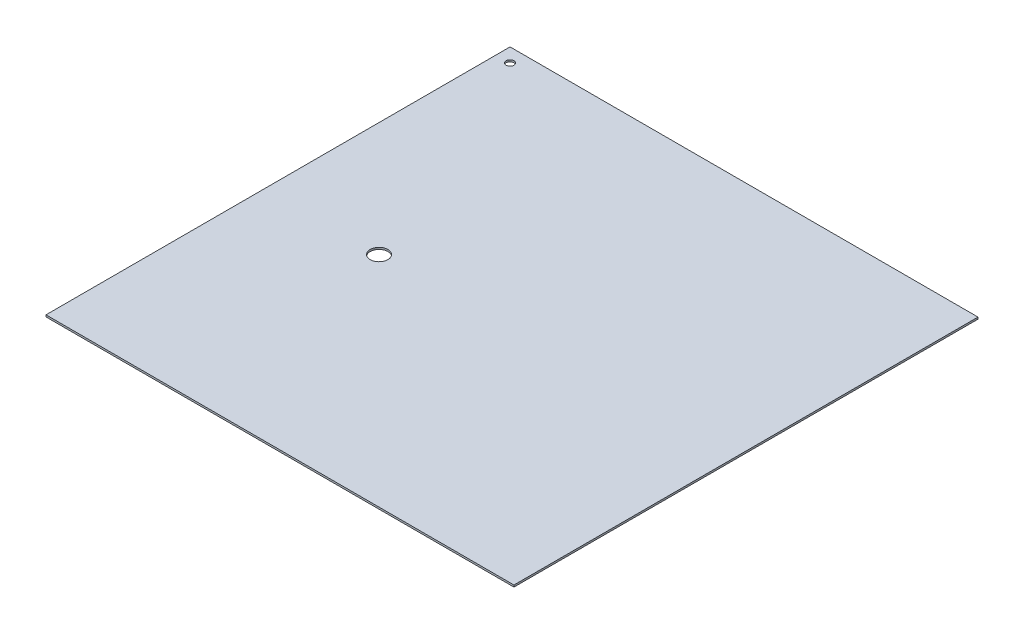
SolidWorks part; units mm, degrees
ref_plane "Front Plane" through (0, 0, 0) normal (0, 0, 1) x (1, 0, 0)
ref_plane "Top Plane" through (0, 0, 0) normal (0, 1, 0) x (1, 0, 0)
ref_plane "Right Plane" through (0, 0, 0) normal (1, 0, 0) x (0, 0, -1)
sketch "Sketch1" plane through (0, 0, 0) normal (0, 0, 1) x (1, 0, 0)
  line L0 (0, 0.3969) -> (0, -0.3969)
  line L1 (-152.4, 0) -> (152.4, 0) construction
  point P6 (0, 0)
  dimension "Width" = 304.8
  dimension "Thk" = 0.7937
sketch "Sketch2" plane through (0, 0, 0) normal (1, 0, 0) x (0, 0, -1)
  line L0 (152.4, 0) -> (-152.4, 0)
  point P4 (0, 0)
  dimension "Length" = 304.8
sketch "Sketch3" plane through (0, 0, 0) normal (0, 0, 1) x (1, 0, 0)
  line L1 (152.4, 0.3969) -> (-152.4, 0.3969)
  line L2 (152.4, 0.3969) -> (152.4, -0.3969)
  line L3 (152.4, -0.3969) -> (-152.4, -0.3969)
  line L4 (-152.4, 0.3969) -> (-152.4, -0.3969)
  line L5 (152.4, 0.3969) -> (-152.4, -0.3969) construction
  line L6 (152.4, -0.3969) -> (-152.4, 0.3969) construction
  point P0 (0, 0)
extrude "Boss-Extrude1" add sketch "Sketch3" along normal up to vertex (152.4 mm away) and the other way up to vertex (152.4 mm away) up to point (0, 0, 152.4) other way up to point (0, 0, -152.4)
sketch "Sketch4" plane through (0, 0.3969, 0) normal (0, 1, 0) x (1, 0, 0)
  line L1 (-49.2783, 105.7329) -> (208.7217, 105.7329)
  line L2 (-49.2783, 105.7329) -> (-49.2783, -94.2671)
  line L3 (-49.2783, -94.2671) -> (208.7217, -94.2671)
  line L4 (208.7217, 105.7329) -> (208.7217, -94.2671)
  line L5 (-49.2783, 105.7329) -> (-49.2783, -94.2671) construction
extrude "Fit2Enclosure" cut sketch "Sketch4" against normal up to next (0.7937 mm away) flip side to cut
hole_wizard "CubeMountHoles" positions "Sketch6" profile "Sketch7" hole size "M3" standard "ANSI Metric" end condition up to next
sketch "Sketch6" plane through (0, 0.3969, 0) normal (0, 1, 0) x (1, 0, 0)
  point P0 (-43.2783, 99.7329)
  point P3 (202.7217, 99.7329)
  point P6 (202.7217, -88.2671)
  point P9 (-122.975, -94)
sketch "Sketch7" plane through (-43.2783, 0.3969, -99.7329) normal (1, 0, 0) x (0, 0, 1)
  line L0 (0, 0) -> (0, 0.7937)
  line L1 (0, 0.7937) -> (1.7, 0.7937)
  line L2 (1.7, 0.7937) -> (1.7, 0)
  line L5 (1.7, 0) -> (0, 0)
  line L11 (0, -6.35) -> (0, 107.95) construction
  dimension "Thru Hole Dia." = 3.4
  dimension "Thru Hole Depth" = 0.7938
sketch "Sketch8" plane through (0, 0.3969, 0) normal (0, 1, 0) x (1, 0, 0)
  line L1 (79.7217, -18.6507) -> (79.7217, -169.8835) construction
  line L2 (-125.4783, 5.7329) -> (14.2217, 5.7329) construction
  circle A0 centre (0, 0) radius 3.81
  dimension "D1" = 7.62
extrude "DrainHole" cut sketch "Sketch8" against normal up to next
ref_plane "SheetTop" through (0, 0.3969, 0) normal (0, 1, 0) x (1, 0, 0)
ref_plane "SheetBottom" through (0, -0.3969, 0) normal (0, -1, 0) x (-1, 0, 0)
ref_axis "DrainHoleAxis" through (0, -0.3969, 0) along (0, 1, 0)
ref_axis "Mnt1" through (-43.2783, -0.3969, -99.7329) along (0, 1, 0)
ref_axis "Mnt2" through (123, -0.3969, -81.0723) along (0, 1, 0)
ref_axis "Mnt3" through (123, -0.3969, 106.9277) along (0, 1, 0)
ref_axis "Mnt4" through (-122.975, -0.3969, 94) along (0, 1, 0)
